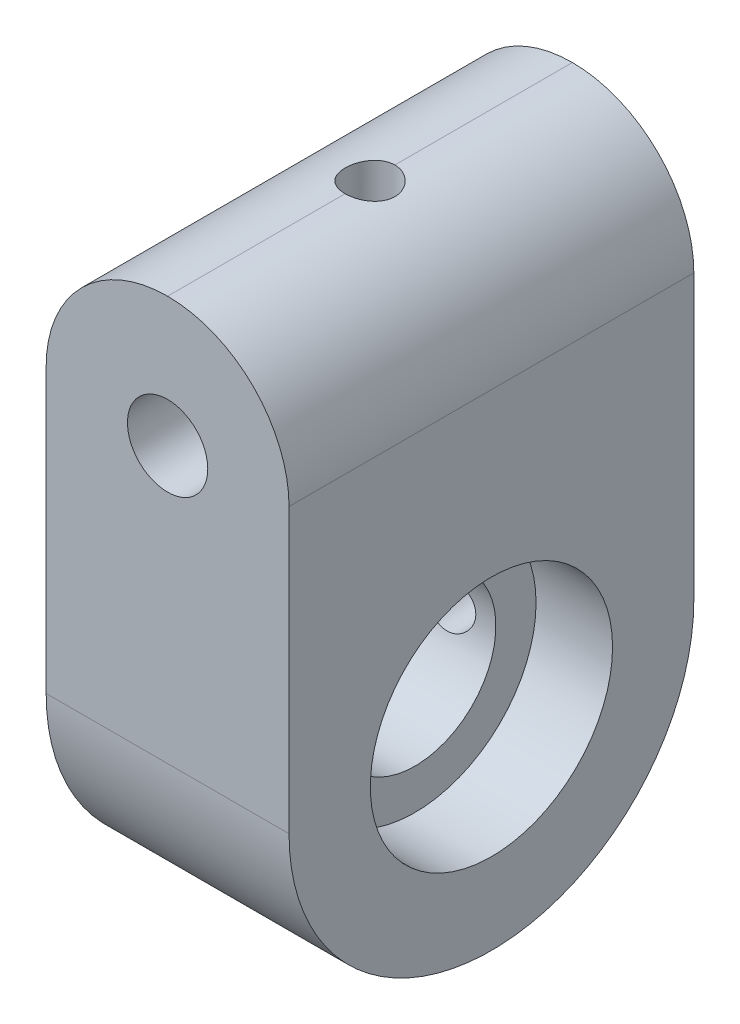
SolidWorks part; units mm, degrees
material "PLA"
ref_plane "Front Plane" through (0, 0, 0) normal (0, 0, 1) x (1, 0, 0)
ref_plane "Top Plane" through (0, 0, 0) normal (0, 1, 0) x (1, 0, 0)
ref_plane "Right Plane" through (0, 0, 0) normal (1, 0, 0) x (0, 0, -1)
sketch "Sketch1" plane through (0, 0, 0) normal (1, 0, 0) x (0, 0, -1)
  circle A0 centre (0, 0) radius 9.5
  circle A1 centre (0, 0) radius 15.875
  dimension "D1" = 19
  dimension "D2" = 31.75
extrude "Boss-Extrude1" add sketch "Sketch1" along normal blind 6
sketch "Sketch2" plane through (0, 0, 0) normal (-1, 0, 0) x (0, 0, 1)
  circle A0 centre (0, 0) radius 6.35
  circle A1 centre (0, 0) radius 15.875
  circle A2 centre (0, 0) radius 15.875
  circle M3 centre (0, 0) radius 15.875
  circle M4 centre (0, 0) radius 9.5
  dimension "D2" = 12.7
  dimension "D1" = 0
extrude "Boss-Extrude2" add sketch "Sketch2" along normal blind 13.05 contours M3 M4 | A0 M4 region at (0, 0, -15.426) region at (0, 0, -9.2313)
sketch "Sketch3" plane through (-13.05, 0, 0) normal (-1, 0, 0) x (0, 0, 1)
  line L0 (0, 15.875) -> (0, -15.875) construction
  line L1 (0, 0) -> (19.648, 0) construction
  circle A0 centre (0, 12.7) radius 1.95
  circle A1 centre (0, 0) radius 15.875
  circle A2 centre (0, 0) radius 15.875
  circle A3 centre (0, -12.7) radius 1.95
  dimension "D2" = 3.9
  dimension "D3" = 12.7
  dimension "D1" = 0
extrude "Cut-Extrude1" cut sketch "Sketch3" against normal blind 10.16 contours A3 | A0 region at (-13.05, 12.7, 0) region at (-13.05, -12.7, 0)
ref_plane "Plane2" through (0, 0, -15.875) normal (0, 0, 1) x (1, 0, 0)
sketch "Sketch5" plane through (0, 0, -15.875) normal (0, 0, 1) x (1, 0, 0)
  line L0 (-13.05, 15.875) -> (-13.05, -15.875) construction
  line L1 (6, -15.875) -> (6, 15.875) construction
  line L2 (-13.05, 15.875) -> (-13.05, -15.875)
  line L3 (6, -15.875) -> (6, 15.875)
  line L4 (-13.05, 0) -> (6, 0) construction
  circle A0 centre (-3.525, 0) radius 1.95
  dimension "D1" = 3.9
extrude "Cut-Extrude3" cut sketch "Sketch5" along normal up to surface (9.525 mm away) contours A0 L4 | L4 A0 region at (-3.525, 0.8276, -15.875) region at (-3.525, -0.8276, -15.875) up to face at (-13.05, 0, 6.35)
sketch "Sketch6" plane through (-13.05, 0, 0) normal (-1, 0, 0) x (0, 0, 1)
  line L0 (0, 0) -> (0, 31.0805) construction
  line L1 (-15.875, 0) -> (-15.875, 31.75)
  line L2 (-15.875, 31.75) -> (15.875, 31.75)
  line L3 (15.875, 0) -> (15.875, 31.75)
  circle A1 centre (0, 0) radius 15.875
  circle A2 centre (0, 0) radius 15.875
  point P9 (0, 31.75)
  circle M6 centre (0, 0) radius 15.875
  dimension "D2" = 31.75
  dimension "D3" = 15.875
  dimension "D1" = 0
extrude "Boss-Extrude3" add sketch "Sketch6" against normal up to surface (19.05 mm away) contours L3 L2 L1 A2 M6 region at (-13.05, 21.7835, 0) up to face at (6, 0, -15.875)
sketch "Sketch7" plane through (0, 0, 15.875) normal (0, 0, 1) x (1, 0, 0)
  line L0 (6, 31.75) -> (-13.05, 31.75) construction
  line L1 (-3.525, 31.75) -> (-3.525, 21.59) construction
  line L2 (6, 0) -> (-13.05, 0) construction
  circle A0 centre (-3.525, 21.59) radius 3.15
  dimension "D1" = 6.3
  dimension "D2" = 21.59
extrude "Cut-Extrude4" cut sketch "Sketch7" against normal up to surface (31.75 mm away) contours A0 region at (-3.525, 21.59, 15.875) up to face at (-3.525, 10.5833, -15.875)
sketch "Sketch8" plane through (0, 31.75, 0) normal (0, 1, 0) x (1, 0, 0)
  line L0 (6, 15.875) -> (-13.05, 15.875) construction
  line L1 (-3.525, 15.875) -> (-3.525, 0) construction
  line L2 (-3.525, 0) -> (6, 0) construction
  line L3 (6, 15.875) -> (6, -15.875) construction
  circle A0 centre (-3.525, 0) radius 1.95
  dimension "D1" = 3.9
extrude "Cut-Extrude5" cut sketch "Sketch8" against normal up to surface (7.01 mm away) contours A0 region at (-3.525, 31.75, 0) up to face at (-0.375, 21.59, -15.875)
fillet "Fillet1" radius 9.525 2 edges at (6, 31.75, 0) (-13.05, 31.75, 0)
sketch "Sketch9" plane through (0, 0, -15.875) normal (0, 0, -1) x (-1, 0, 0)
  line L0 (1.575, 0) -> (5.475, 0) construction
  circle A0 centre (3.525, 0) radius 1.95
  dimension "D1" = 3.9
extrude "Cut-Extrude6" cut sketch "Sketch9" against normal up to surface (22.225 mm away) up to face at (0, 0, 6.35)
